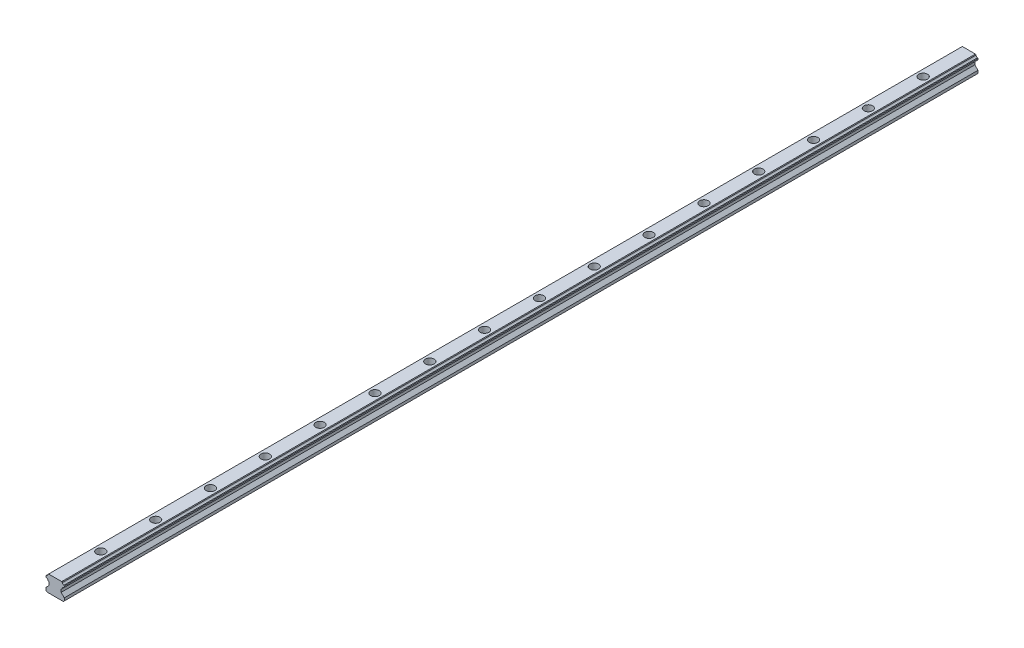
SolidWorks part; units mm, degrees
material "Plain Carbon Steel"
ref_plane "Front Plane" through (0, 0, 0) normal (0, 0, 1) x (1, 0, 0)
ref_plane "Top Plane" through (0, 0, 0) normal (0, 1, 0) x (1, 0, 0)
ref_plane "Right Plane" through (0, 0, 0) normal (1, 0, 0) x (0, 0, -1)
sketch "Sketch1" plane through (0, 0, 0) normal (0, 0, 1) x (1, 0, 0)
  line L0 (0, 13.3681) -> (0, -3.2505) construction
  line L1 (-6.55, 1.465) -> (-6.55, -1.465)
  line L2 (-6.55, 0) -> (0, 0) construction
  line L3 (-6.55, -1.465) -> (-10, -4.915)
  line L4 (-10, -4.915) -> (-10, -7.915)
  line L5 (-10, -7.915) -> (-9, -8.915)
  line L6 (-9, -8.915) -> (0, -8.915)
  line L7 (-6.55, 1.465) -> (-7.7681, 2.6831)
  line L8 (-10, 4.915) -> (-10, 6.245)
  line L9 (-10, 6.245) -> (-9.4697, 6.7753)
  line L10 (-7.16, 9.085) -> (0, 9.085)
  line L11 (-10, 4.915) -> (-10, -4.915) construction
  line L12 (-10, 5.58) -> (0, 5.58) construction
  line L13 (-7.7681, 8.4769) -> (-7.16, 9.085)
  line L14 (-9.4697, 4.3847) -> (-10, 4.915)
  line L15 (0, 9.085) -> (0, -8.915)
  arc A0 (-9.4697, 6.7753) -> (-7.7681, 8.4769) centre (-9.7486, 8.7558) ccw
  arc A1 (-9.4697, 4.3847) -> (-7.7681, 2.6831) centre (-9.7486, 2.4042) cw
  dimension "D10" = 4
  dimension "D1" = 2.93
  dimension "D2" = 6.55
  dimension "D3" = 9
  dimension "D4" = 7.16
  dimension "D5" = 3
  dimension "D6" = 1.33
  dimension "D7" = 18
  dimension "D8" = 45
  dimension "D9" = 45
  dimension "D11" = 0.75
  dimension "D12" = 0.86
extrude "Boss-Extrude1" add sketch "Sketch1" along normal blind 500
mirror "Mirror1" about plane through (0, 9.085, 500) normal (-1, 0, 0) of "Boss-Extrude1"
sketch "Sketch2" plane through (0, 9.085, 0) normal (0, 1, 0) x (1, 0, 0)
  line L0 (0, 130.187) -> (0, 31.9327) construction
  line L1 (7.16, 0) -> (-7.16, 0) construction
  circle A0 centre (0, -30) radius 3
  dimension "D1" = 6
  dimension "D2" = 30
extrude "Cut-Extrude1" cut sketch "Sketch2" against normal through all
sketch "Sketch3" plane through (0, 9.085, 0) normal (0, 1, 0) x (1, 0, 0)
  circle A0 centre (0, -30) radius 4.75
  dimension "D1" = 9.5
extrude "Cut-Extrude2" cut sketch "Sketch3" against normal blind 8.5
pattern_linear "LPattern1" count 100 spacing 60 along (0, 0, 1) of "Cut-Extrude1", "Cut-Extrude2"
mirror "Mirror2" about plane through (-9.7486, 2.4042, 0) normal (0, 0, -1) of bodies 106
equation "\"length\"= 1000mm"
equation "\"D1@Boss-Extrude1\" = ( \"work_area_width\" - 100 ) / 2"
equation "\"M5_tap\"=4.2mm"
equation "\"M5_clearence\"=5.5mm"
equation "\"M6_tap\"=5mm"
equation "\"M6_clearence\"=6.6mm"
equation "\"work_area_width\"=1100mm"
equation "\"work_area_depth\"=1000mm"
